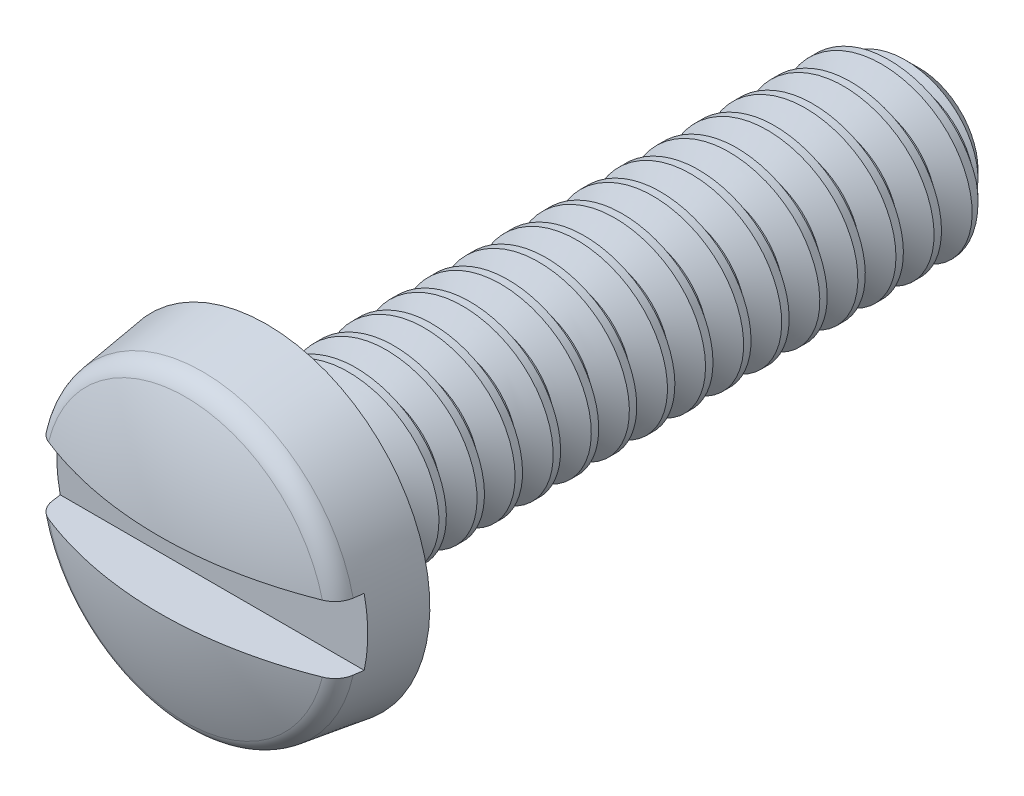
SolidWorks part; units mm, degrees
ref_plane "Front" through (0, 0, 0) normal (0, 0, 1) x (1, 0, 0)
ref_plane "Top" through (0, 0, 0) normal (0, 1, 0) x (1, 0, 0)
ref_plane "Right" through (0, 0, 0) normal (1, 0, 0) x (0, 0, -1)
sketch "Sketch1" plane through (0, 0, 0) normal (0, 0, 1) x (1, 0, 0)
  circle A0 centre (0, 0) radius 1.5
  dimension "Head Dia" = 3
extrude "Extrude3" add sketch "Sketch1" along normal blind 1
sketch "Sketch11" plane through (0, 0, 0) normal (1, 0, 0) x (0, 0, -1)
  line L0 (0, 0) -> (-1.254, 0) construction
  line L4 (-1, 1.5) -> (-1, -1.5) construction
  line L5 (-1.254, 1.56) -> (0, 1.56)
  line L7 (0, 1.56) -> (0, 1.5)
  line L8 (-0.5884, 1.4173) -> (0, 1.5)
  line L9 (0, -1.5) -> (0, 1.5) construction
  line L13 (-1, 0) -> (-1.254, 0)
  line L14 (-1.254, 0) -> (-1.254, 1.56)
  arc A0 (-0.7457, 1.2949) -> (-1, 0) centre (2.4242, 0) ccw
  arc A1 (-0.5884, 1.4173) -> (-0.7457, 1.2949) centre (-0.5606, 1.2193) ccw
  point P13 (-0.7, 1.4016)
  dimension "D1" = 0.2
  dimension "D3" = 0.254
  dimension "D5" = 0.06
  dimension "D2" = 0.3
  dimension "D4" = 8
revolve "Cut-Revolve3" cut sketch "Sketch11" angle 360 about L0
sketch "Sketch4" plane through (0, 0, 0) normal (1, 0, 0) x (0, 0, -1)
  line L0 (0, 0) -> (6, 0)
  line L3 (6, 0) -> (6, 0.8)
  line L4 (6, 0.8) -> (0, 0.8)
  line L6 (0, 0.8) -> (0, 0)
  line L9 (6, 0.8) -> (6, -0.8) construction
  dimension "length" = 6
  dimension "dia" = 1.6
revolve "Revolve1" add sketch "Sketch4" angle 360 about L0
sketch "Sketch13" plane through (0, 0, -6) normal (0, 0, -1) x (-1, 0, 0)
  circle A2 centre (0, 0) radius 0.8
curve "Helix/Spiral1" pitch 0.35 height 6 radius 0.8 centre (0, 0, -6) axis (0, 0, 1) start towards (0, 1, 0)
chamfer "Chamfer2" distance 0.2625 angle 45 1 edges at (0.8, 0, -6)
sketch "Sketch14" plane through (0, 0, 0) normal (1, 0, 0) x (0, 0, -1)
  line L0 (6, 0.8219) -> (6.3063, 0.8219)
  line L1 (6.3063, 0.8219) -> (6.175, 0.5851)
  line L2 (6.175, 0.5851) -> (6.1313, 0.5851)
  line L3 (6.1313, 0.5851) -> (6, 0.8219)
  line L4 (6.0656, 0.7035) -> (6.2406, 0.7035) construction
  line L5 (6, 0.8) -> (0, 0.8) construction
  dimension "D1" = 0.0437
  dimension "D2" = 58
  dimension "D3" = 0.175
  dimension "D4" = 0.0219
sweep "Cut-Sweep1" cut profiles "Sketch14" path "Helix/Spiral1" align with end faces yes
ref_plane "Plane1" through (0, 0, 32.1) normal (0, 0, -1) x (-1, 0, 0)
sketch "Sketch29" [suppressed] plane through (0, 0, 28.575) normal (0, 0, -1) x (-1, 0, 0)
  circle A0 centre (0, 0) radius 1.7526 construction
  circle A1 centre (0, 0) radius 1.7526
  point P3 (0, -1.7526)
  point P4 (0, 1.7526)
extrude "Extrude11" [suppressed] add sketch "Sketch29" against normal up to surface (28.575 mm away) up to plane "Front"
ref_plane "Plane2" through (0, 0, 1) normal (0, 0, 1) x (1, 0, 0)
sketch "Sketch32" plane through (0, 0, 1) normal (0, 0, 1) x (1, 0, 0)
  line L0 (-1.5, 0.3062) -> (1.5, -0.3062) construction
  line L1 (-1.5, 0.3062) -> (1.5, 0.3063)
  line L2 (-1.5, 0.3062) -> (-1.5, -0.3063)
  line L3 (-1.5, -0.3063) -> (1.5, -0.3062)
  line L4 (1.5, 0.3063) -> (1.5, -0.3062)
  circle A0 centre (0, 0) radius 1.5 construction
  dimension "D1" = 0.6125
extrude "Extrude16" cut sketch "Sketch32" against normal blind 0.5
sketch "Sketch18" plane through (0, 0, 0) normal (1, 0, 0) x (0, 0, -1)
  line L1 (6, 0.8) -> (0, 0.8) construction
  point P0 (5.475, -0.8)
  point P1 (5.65, 0.8)
  point P2 (-1, 0.3063)
  dimension "D1" = 0.35
  dimension "D2" = 0.525
equation "\"D3@Helix/Spiral1\" = \"length@Sketch4\""
equation "\"D1@Sketch14\" = \"D4@Helix/Spiral1\" * .125"
equation "\"D3@Sketch14\" = \"D4@Helix/Spiral1\" * .5"
equation "\"D5@Sketch11\" = \"Head Dia@Sketch1\" * .02"
equation "\"D1@Chamfer2\" = \"D4@Helix/Spiral1\" * .75"
equation "\"D1@Sketch18\" = \"D4@Helix/Spiral1\""
equation "\"D2@Sketch18\" = \"D4@Helix/Spiral1\" * 1.5"
equation "\"D2@Sketch11\" = \"Head Ht@Extrude3\" * .3"
equation "\"D1@Extrude16\" = \"Head Ht@Extrude3\" * .5"
equation "\"D1@Sketch11\" = \"Head Ht@Extrude3\" * .2"
equation "\"D4@Sketch14\" = \"D1@Sketch14\" * .5"
equation "\"D1@Sketch32\" = \"D4@Helix/Spiral1\" * 1.75"
